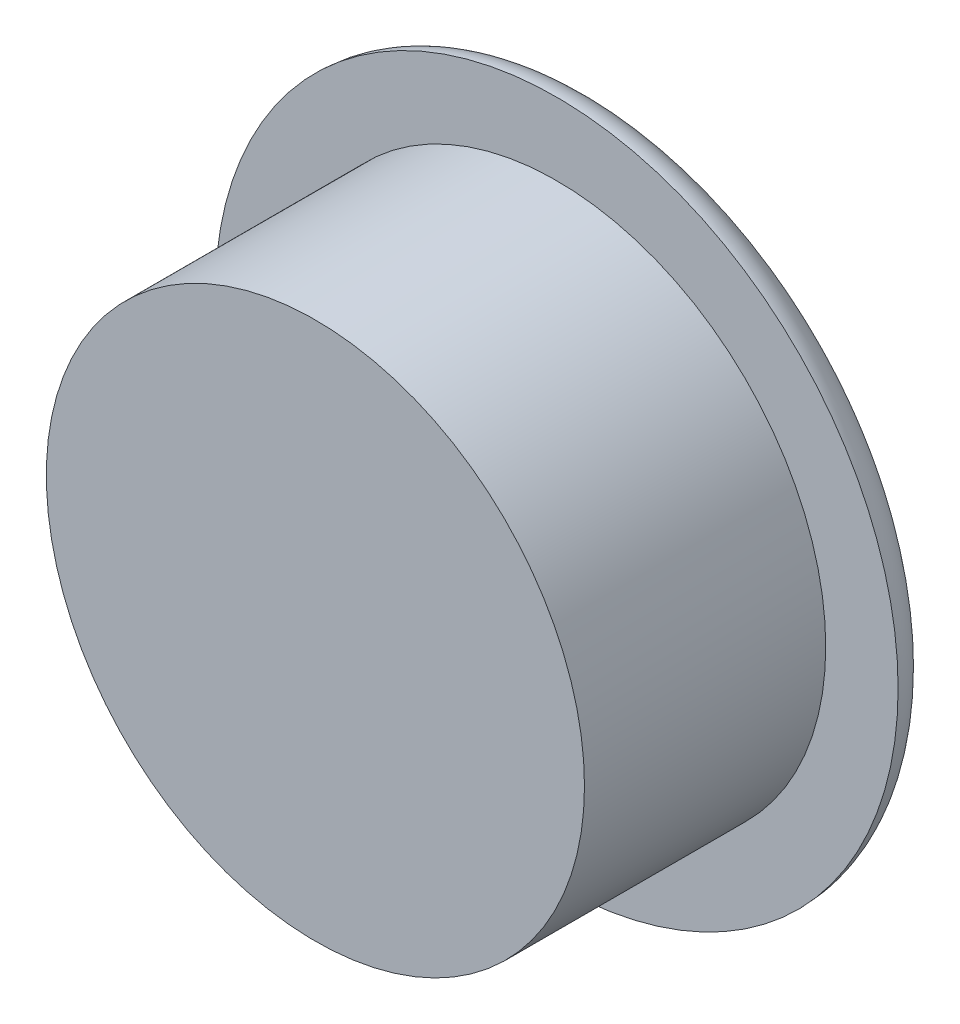
SolidWorks part; units mm, degrees
ref_plane "Front Plane" through (0, 0, 0) normal (0, 0, 1) x (1, 0, 0)
ref_plane "Top Plane" through (0, 0, 0) normal (0, 1, 0) x (1, 0, 0)
ref_plane "Right Plane" through (0, 0, 0) normal (1, 0, 0) x (0, 0, -1)
sketch "Sketch6" plane through (0, 0, 0) normal (0, 0, 1) x (1, 0, 0)
  circle A0 centre (0, 0) radius 18.4
extrude "Boss-Extrude3" add sketch "Sketch6" along normal blind 2
sketch "Sketch7" plane through (0, 0, 0) normal (0, 0, 1) x (1, 0, 0)
  circle A0 centre (0, 0) radius 14.5
extrude "Boss-Extrude4" add sketch "Sketch7" along normal blind 15
fillet "Fillet12" radius 2 1 edges at (18.4, 0, 0)
